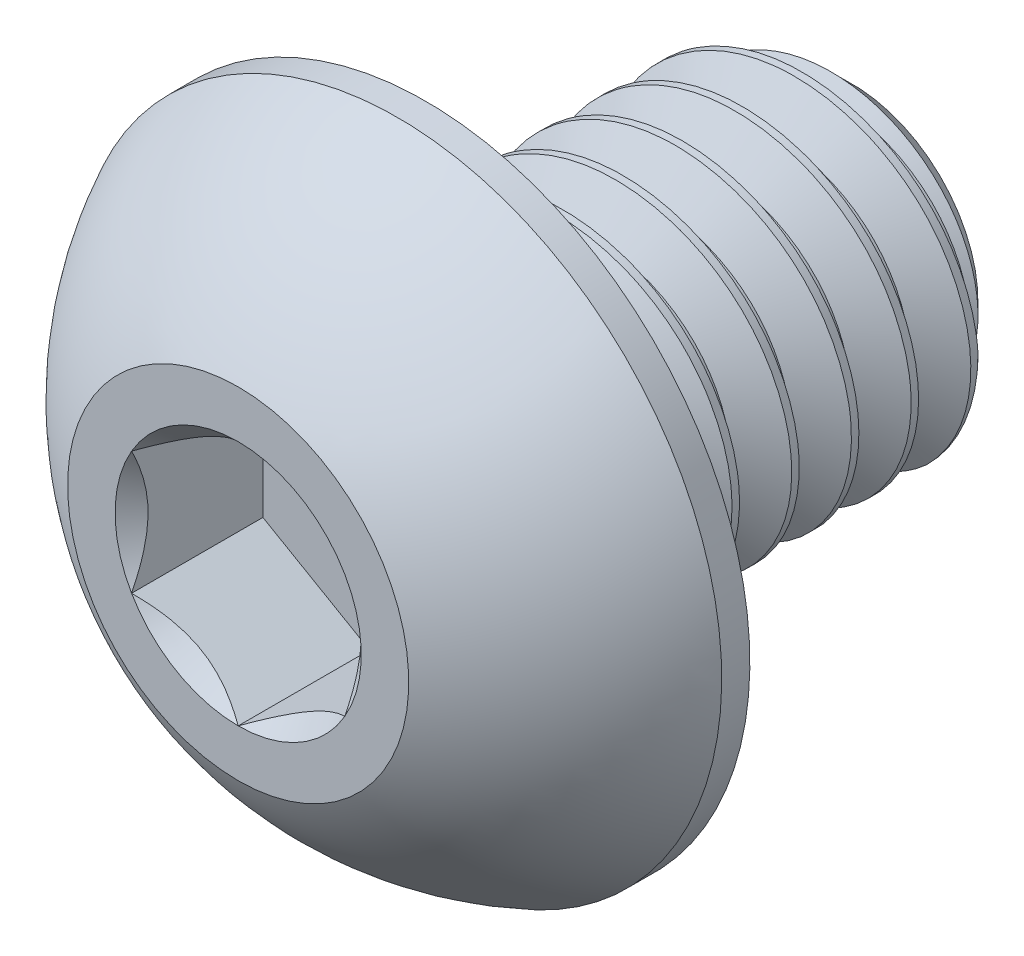
SolidWorks part; units mm, degrees
ref_plane "Front" through (0, 0, 0) normal (0, 0, 1) x (1, 0, 0)
ref_plane "Top" through (0, 0, 0) normal (0, 1, 0) x (1, 0, 0)
ref_plane "Right" through (0, 0, 0) normal (1, 0, 0) x (0, 0, -1)
sketch "Sketch1" plane through (0, 0, 0) normal (1, 0, 0) x (0, 0, -1)
  line L2 (-2.5, 2) -> (2.5, 2)
  line L3 (2.5, 2) -> (2.5, 0)
  line L4 (2.5, 0) -> (-2.5, 0)
  line L6 (-2.83, 3.8) -> (-2.5, 3.8) construction
  line L7 (2.5, 2) -> (2.5, -2) construction
  line L8 (-4.7, 0) -> (-2.5, 0) construction
  line L9 (-2.5, 3.8) -> (-2.5, -3.8) construction
  line L11 (-2.5, 2) -> (-2.5, 0)
  line L13 (-4.7, 1.25) -> (-4.7, -1.25) construction
  line L14 (-4.7, 1.25) -> (-4.7, 2) construction
  line L15 (2.4563, 2.0758) -> (2.8063, 1.4696) construction
  line L16 (2.8063, 1.4696) -> (3.1563, 2.0758) construction
  line L17 (3.1563, 2.0758) -> (2.4563, 2.0758) construction
  line L18 (2.5, 2) -> (3.1125, 2) construction
  line L19 (2.8063, 2.0758) -> (2.8063, 2) construction
  line L20 (2.8063, 2) -> (2.8063, 1.5453) construction
  line L21 (2.8063, 1.5453) -> (2.8063, 1.4696) construction
  line L22 (2.7625, 1.5453) -> (2.85, 1.5453)
  line L23 (2.4781, 2.0379) -> (3.1344, 2.0379)
  line L24 (2.85, 1.5453) -> (3.1344, 2.0379)
  line L25 (2.7625, 1.5453) -> (2.4781, 2.0379)
  line L26 (1.975, 2) -> (2.5, 1.475)
  arc A3 (-4.7, 2) -> (-2.83, 3.8) centre (-0.9736, 0) cw construction
  point P29 (2.8063, 2.0379)
  point P30 (0.75, -2)
  point P33 (0, 0)
  dimension "Thread Size" = 4
  dimension "D1" = 0.33
  dimension "Head Height" = 2.2
  dimension "Head Diameter" = 7.6
  dimension "Length" = 5
  dimension "Drive Size" = 2.5
  dimension "Thread Pitch" = 0.7
  dimension "D3" = 0.0875
  dimension "D2" = 0.525
  dimension "D4" = 45
  dimension "D5" = 1.75
sketch "Sketch10" plane through (0, 0, 0) normal (1, 0, 0) x (0, 0, -1)
  line L0 (1.975, 2) -> (2.5, 1.475) construction
  line L1 (1.975, 2) -> (2.5, 1.475)
  line L4 (2.5, 2) -> (-2.5, 2)
  line L5 (2.5, 0) -> (2.5, 2)
  line L6 (-2.5, 0) -> (2.5, 0)
  line L7 (-2.5, 2) -> (-2.5, 0)
  line L8 (1.975, 2) -> (-2.5, 2)
  line L9 (2.5, 0) -> (2.5, 1.475)
  line L10 (-2.5, 0) -> (2.5, 0)
  line L11 (-2.5, 2) -> (-2.5, 0)
  dimension "D1" = 0
revolve "Revolve3" add sketch "Sketch10" angle 360 about L8
sketch "Sketch7" plane through (0, 0, 0) normal (1, 0, 0) x (0, 0, -1)
  line L6 (-2.83, 3.8) -> (-2.5, 3.8) construction
  line L8 (-4.7, 0) -> (-2.5, 0) construction
  line L11 (-2.5, 3.8) -> (-2.5, -3.8) construction
  line L12 (-2.83, 3.8) -> (-2.5, 3.8)
  line L13 (-4.7, 0) -> (-2.5, 0)
  line L14 (-4.7, 1.25) -> (-4.7, -1.25) construction
  line L15 (-2.5, 3.8) -> (-2.5, 0)
  line L16 (-4.7, 2) -> (-4.7, 0)
  arc A2 (-2.83, 3.8) -> (-4.7, 2) centre (-0.9736, 0) ccw construction
  arc A3 (-2.83, 3.8) -> (-4.7, 2) centre (-0.9736, 0) ccw
revolve "Revolve2" add sketch "Sketch7" angle 360 mid plane about L13
sketch "Sketch5" plane through (0, 0, 4.7) normal (0, 0, 1) x (1, 0, 0)
  line L1 (1.25, -0.7217) -> (1.25, 0.7217)
  line L2 (1.25, 0.7217) -> (0, 1.4434)
  line L3 (0, 1.4434) -> (-1.25, 0.7217)
  line L4 (-1.25, 0.7217) -> (-1.25, -0.7217)
  line L5 (-1.25, -0.7217) -> (0, -1.4434)
  line L6 (0, -1.4434) -> (1.25, -0.7217)
  circle A0 centre (0, 0) radius 1.25 construction
extrude "Cut-Extrude2" cut sketch "Sketch5" against normal blind 1.54
sketch "Sketch6" plane through (0, 0, 4.7) normal (0, 0, 1) x (1, 0, 0)
  circle A0 centre (0, 0) radius 1.4434
extrude "Cut-Extrude3" cut sketch "Sketch6" against normal blind 1.54 draft 45
sketch "Sketch9" plane through (0, 0, 2.5) normal (0, 0, -1) x (-1, 0, 0)
  circle A0 centre (0, 0) radius 2 construction
  circle A4 centre (0, 0) radius 2
split "Split1" bodies to split 113 resulting bodies 123 124 split by face at (0, -3.8, 2.5)
sketch "Sketch11" plane through (0, 0, -2.5) normal (0, 0, -1) x (-1, 0, 0)
  circle A0 centre (0, 0) radius 2 construction
  circle A1 centre (0, 0) radius 2
curve "Helix/Spiral1" pitch 0.7 height 7.2 radius 2 centre (0, 0, -2.5) axis (0, 0, 1) start towards (0, 1, 0)
sketch "Sketch12" plane through (0, 0, 0) normal (1, 0, 0) x (0, 0, -1)
  line L0 (2.7625, 1.5453) -> (2.85, 1.5453) construction
  line L1 (2.85, 1.5453) -> (3.1344, 2.0379) construction
  line L2 (2.4781, 2.0379) -> (3.1344, 2.0379) construction
  line L3 (2.7625, 1.5453) -> (2.4781, 2.0379) construction
  line L4 (2.7625, 1.5453) -> (2.85, 1.5453)
  line L5 (2.85, 1.5453) -> (3.1344, 2.0379)
  line L6 (2.4781, 2.0379) -> (3.1344, 2.0379)
  line L7 (2.7625, 1.5453) -> (2.4781, 2.0379)
sweep "Cut-Sweep2" cut profiles "Sketch12" path "Helix/Spiral1" align with end faces yes
extrude "Boss-Extrude1" add sketch "Sketch9" along normal blind 10 draft 45
equation "\"D1@Cut-Extrude2\" = \"Head Height@Sketch1\" * .7"
equation "\"D1@Sketch1\" = \"Head Height@Sketch1\" * .15"
equation "\"D1@Cut-Extrude3\" = \"D1@Cut-Extrude2\""
equation "\"D3@Sketch1\" = \"Thread Pitch@Sketch1\" / 8"
equation "\"D2@Sketch1\" = \"Thread Pitch@Sketch1\" * 0.75"
equation "\"D3@Helix/Spiral1\" = \"Length@Sketch1\" + \"Head Height@Sketch1\""
equation "\"D4@Helix/Spiral1\" = \"Thread Pitch@Sketch1\""
equation "\"D5@Sketch1\" = \"Thread Pitch@Sketch1\" * 2.5"
